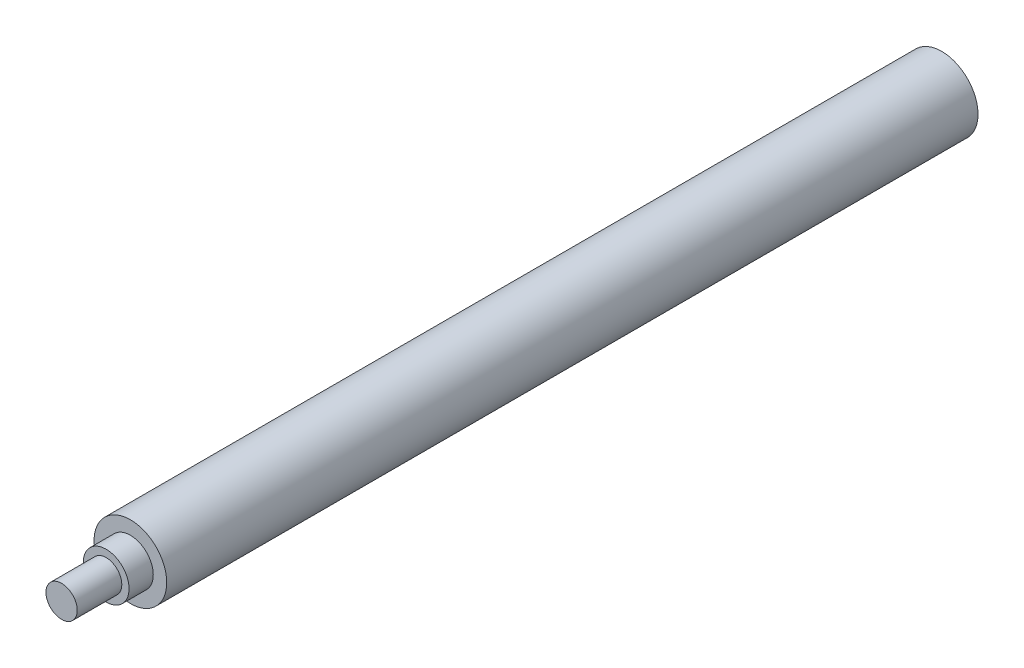
SolidWorks part; units mm, degrees
ref_plane "Front Plane" through (0, 0, 0) normal (0, 0, 1) x (1, 0, 0)
ref_plane "Top Plane" through (0, 0, 0) normal (0, 1, 0) x (1, 0, 0)
ref_plane "Right Plane" through (0, 0, 0) normal (1, 0, 0) x (0, 0, -1)
sketch "Sketch1" plane through (0, 0, 0) normal (0, 1, 0) x (1, 0, 0)
  line L0 (4.7625, 104.775) -> (-4.7625, 104.775) construction
  line L1 (24.145, -10.6045) -> (-24.145, -10.6045) construction
  line L2 (2.05, -1.5875) -> (2.05, -10.6045) construction
  line L3 (24.145, -4.7625) -> (-24.145, -4.7625) construction
  line L4 (3, -1.5875) -> (3, -4.7625) construction
  line L5 (4.7625, -1.5875) -> (-4.7625, -1.5875) construction
  line L6 (0, -1.5875) -> (0, 104.775) construction
  line L7 (4.7625, -1.5875) -> (4.7625, 104.775) construction
  line L8 (4.7625, 104.775) -> (0, 104.775)
  line L9 (2.05, -10.6045) -> (0, -10.6045)
  line L10 (2.05, -4.7625) -> (2.05, -10.6045)
  line L11 (3, -4.7625) -> (2.05, -4.7625)
  line L12 (3, -1.5875) -> (3, -4.7625)
  line L13 (4.7625, -1.5875) -> (3, -1.5875)
  line L14 (0, -10.6045) -> (0, 104.775)
  line L15 (4.7625, -1.5875) -> (4.7625, 104.775)
revolve "Revolve1" add sketch "Sketch1" angle 360 about L14
